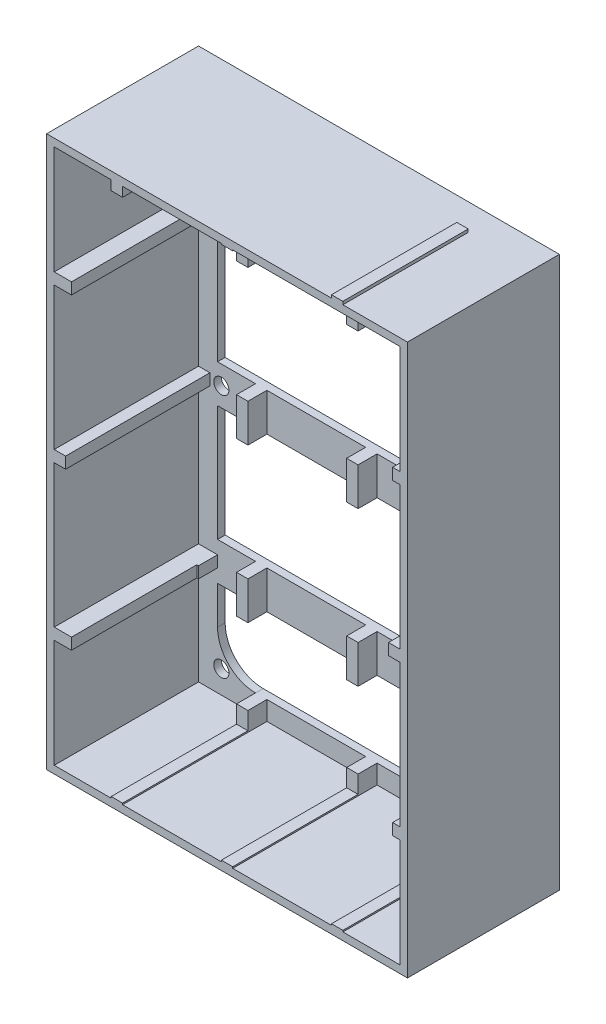
SolidWorks part; units mm, degrees
ref_plane "前视基准面" through (0, 0, 0) normal (0, 0, 1) x (1, 0, 0)
ref_plane "上视基准面" through (0, 0, 0) normal (0, 1, 0) x (1, 0, 0)
ref_plane "右视基准面" through (0, 0, 0) normal (1, 0, 0) x (0, 0, -1)
sketch "Sketch1" plane through (0, 0, 0) normal (0, 0, 1) x (1, 0, 0)
  line L1 (-47.5, 72.5) -> (47.5, 72.5)
  line L2 (-47.5, 72.5) -> (-47.5, -72.5)
  line L3 (-47.5, -72.5) -> (47.5, -72.5)
  line L4 (47.5, 72.5) -> (47.5, -72.5)
  line L5 (-47.5, 72.5) -> (47.5, -72.5) construction
  line L6 (-47.5, -72.5) -> (47.5, 72.5) construction
  point P0 (0, 0)
  dimension "D1" = 95
  dimension "D2" = 145
extrude "Boss-Extrude1" add sketch "Sketch1" along normal mid plane 40
sketch "Sketch2" plane through (0, 0, 20) normal (0, 0, 1) x (1, 0, 0)
  line L8 (45.5, -70.5) -> (45.5, 70.5)
  line L9 (45.5, 70.5) -> (-45.5, 70.5)
  line L10 (-45.5, 70.5) -> (-45.5, -70.5)
  line L11 (-45.5, -70.5) -> (45.5, -70.5)
  line L12 (45.5, -70.5) -> (45.5, 70.5)
  line L13 (45.5, 70.5) -> (-45.5, 70.5)
  line L14 (-45.5, 70.5) -> (-45.5, -70.5)
  line L15 (-45.5, -70.5) -> (45.5, -70.5)
  dimension "D1" = 2
extrude "Cut-Extrude1" cut sketch "Sketch2" against normal blind 40
ref_plane "Base" through (0, 0, -20) normal (0, 0, -1) x (-1, 0, 0)
sketch "Sketch3" plane through (0, 0, -20) normal (0, 0, -1) x (-1, 0, 0)
  line L0 (-45.5, 70.5) -> (45.5, 70.5) construction
  line L2 (42.5, -70.5) -> (42.5, 70.5) construction
  line L4 (-42.5, -70.5) -> (-42.5, 70.5) construction
  line L5 (42.5, -70.5) -> (-42.5, 70.5) construction
  line L6 (42.5, 70.5) -> (-42.5, -70.5) construction
  line L7 (-40.5, -35.5) -> (40.5, -35.5)
  line L8 (-40.5, -45.5) -> (40.5, -45.5)
  line L9 (-40.5, 5) -> (40.5, 5)
  line L10 (-40.5, -5) -> (40.5, -5)
  line L11 (45.5, -70.5) -> (-45.5, -70.5) construction
  line L12 (45.5, 70.5) -> (45.5, -70.5) construction
  line L13 (-45.5, -70.5) -> (-45.5, 70.5) construction
  line L14 (45.5, -70.5) -> (-45.5, -70.5)
  line L15 (-40.5, -65.5) -> (40.5, -65.5)
  line L16 (40.5, 65.5) -> (-40.5, 65.5)
  line L17 (40.5, -65.5) -> (40.5, 65.5)
  line L18 (-40.5, 65.5) -> (-40.5, -65.5)
  line L19 (-30.5, -65.5) -> (30.5, -65.5)
  line L20 (30.5, 65.5) -> (-30.5, 65.5)
  line L21 (40.5, -55.5) -> (40.5, -45.5)
  line L22 (-40.5, 55.5) -> (-40.5, 45.5)
  line L23 (45.5, 70.5) -> (45.5, -70.5)
  line L24 (-45.5, -70.5) -> (-45.5, 70.5)
  line L25 (-45.5, 70.5) -> (45.5, 70.5)
  line L26 (-40.5, 45.5) -> (40.5, 45.5)
  line L27 (-40.5, 35.5) -> (40.5, 35.5)
  line L28 (-62.7216, 0) -> (91.8842, 0) construction
  line L29 (-40.5, 35.5) -> (-40.5, 5)
  line L30 (40.5, 45.5) -> (40.5, 55.5)
  line L31 (40.5, 5) -> (40.5, 35.5)
  line L32 (-40.5, -5) -> (-40.5, -35.5)
  line L33 (-40.5, -45.5) -> (-40.5, -55.5)
  line L34 (40.5, -35.5) -> (40.5, -5)
  arc A0 (-30.5, -65.5) -> (-40.5, -55.5) centre (-30.5, -55.5) cw
  arc A1 (30.5, -65.5) -> (40.5, -55.5) centre (30.5, -55.5) ccw
  arc A2 (30.5, 65.5) -> (40.5, 55.5) centre (30.5, 55.5) cw
  arc A3 (-30.5, 65.5) -> (-40.5, 55.5) centre (-30.5, 55.5) ccw
  point P0 (0, 0)
  dimension "D3" = 10
  dimension "D1" = 85
  dimension "D4" = 10
  dimension "D5" = 20
  dimension "D6" = 5
  dimension "D2" = 5
extrude "Boss-Extrude2" add sketch "Sketch3" against normal blind 2
sketch "Sketch4" plane through (0, 0, -20) normal (0, 0, -1) x (-1, 0, 0)
  line L0 (-47.5, 72.5) -> (47.5, 72.5) construction
  line L1 (-47.5, -72.5) -> (-47.5, 72.5) construction
  line L2 (47.5, 72.5) -> (47.5, -72.5) construction
  line L3 (-75.8795, 0) -> (73.4613, 0) construction
  line L4 (47.5, 72.5) -> (47.5, -72.5) construction
  line L5 (-42.5, -70) -> (42.5, -70) construction
  line L6 (-42.5, -70) -> (-42.5, 70) construction
  line L7 (-42.5, 70) -> (42.5, 70) construction
  line L8 (42.5, -70) -> (42.5, 70) construction
  line L9 (-42.5, -70) -> (42.5, 70) construction
  line L10 (-42.5, 70) -> (42.5, -70) construction
  line L11 (-47.5, -72.5) -> (-47.5, 72.5) construction
  circle A0 centre (-39.5, 64.5) radius 2
  circle A1 centre (39.5, 64.5) radius 2
  circle A4 centre (-39.5, 0) radius 2
  circle A5 centre (39.5, 0) radius 2
  circle A6 centre (-39.5, -64.5) radius 2
  circle A7 centre (39.5, -64.5) radius 2
  point P21 (0, 0)
  dimension "D1" = 8
  dimension "D5" = 85
  dimension "D2" = 8
  dimension "D3" = 8
  dimension "D4" = 8
  dimension "D6" = 140
  dimension "D7" = 8
  dimension "D8" = 8
extrude "Cut-Extrude2" cut sketch "Sketch4" against normal up to next
sketch "Sketch6" plane through (0, 0, -18) normal (0, 0, 1) x (1, 0, 0)
  line L0 (-45.5, 70.5) -> (45.5, 70.5) construction
  line L1 (42.5, -68) -> (-42.5, -68) construction
  line L2 (42.5, -68) -> (42.5, 68) construction
  line L3 (42.5, 68) -> (-42.5, 68) construction
  line L4 (-42.5, -68) -> (-42.5, 68) construction
  line L5 (-30.5, 65.5) -> (30.5, 65.5) construction
  line L6 (-30.5, 68) -> (-27.5, 68)
  line L7 (-30.5, 70.5) -> (-27.5, 70.5)
  line L8 (-30.5, 70.5) -> (-30.5, 68)
  line L9 (-30.5, 68) -> (-27.5, 68)
  line L10 (-27.5, 70.5) -> (-27.5, 68)
  line L11 (0, 86.8311) -> (0, -114.9189) construction
  line L12 (-76.1678, 0) -> (120.2613, 0) construction
  line L13 (30.5, 68) -> (27.5, 68)
  line L14 (27.5, 70.5) -> (27.5, 68)
  line L15 (30.5, 70.5) -> (27.5, 70.5)
  line L16 (30.5, 70.5) -> (30.5, 68)
  line L17 (30.5, -70.5) -> (30.5, -68)
  line L18 (-1.5, 70.5) -> (1.5, 70.5)
  line L19 (-1.5, 70.5) -> (-1.5, 68)
  line L20 (-1.5, 68) -> (1.5, 68)
  line L21 (1.5, 70.5) -> (1.5, 68)
  line L22 (30.5, -70.5) -> (27.5, -70.5)
  line L23 (27.5, -70.5) -> (27.5, -68)
  line L24 (30.5, -68) -> (27.5, -68)
  line L25 (-1.5, -68) -> (1.5, -68)
  line L26 (1.5, -70.5) -> (1.5, -68)
  line L27 (-1.5, -70.5) -> (1.5, -70.5)
  line L28 (-1.5, -70.5) -> (-1.5, -68)
  line L29 (-30.5, -68) -> (-27.5, -68)
  line L30 (-27.5, -70.5) -> (-27.5, -68)
  line L31 (-30.5, -70.5) -> (-27.5, -70.5)
  line L32 (-30.5, -70.5) -> (-30.5, -68)
  line L33 (-45.5, 70.5) -> (-45.5, -70.5) construction
  line L34 (-45.5, 42) -> (-42.5, 42)
  line L35 (-45.5, 42) -> (-45.5, 39)
  line L36 (-45.5, 39) -> (-42.5, 39)
  line L37 (-42.5, 42) -> (-42.5, 39)
  line L38 (-45.5, -70.5) -> (-45.5, 70.5) construction
  line L39 (-45.5, 1.5) -> (-42.5, 1.5)
  line L40 (-45.5, 1.5) -> (-45.5, -1.5)
  line L41 (-45.5, -1.5) -> (-42.5, -1.5)
  line L42 (-42.5, 1.5) -> (-42.5, -1.5)
  line L43 (-33.759, -35.5) -> (-33.759, -45.5) construction
  line L44 (-45.5, -39) -> (-42.5, -39)
  line L45 (-45.5, -39) -> (-45.5, -42)
  line L46 (-45.5, -42) -> (-42.5, -42)
  line L47 (-42.5, -39) -> (-42.5, -42)
  line L48 (40.5, -35.5) -> (-40.5, -35.5) construction
  line L49 (-40.5, -45.5) -> (40.5, -45.5) construction
  line L50 (-33.759, 5) -> (-33.759, -5) construction
  line L51 (40.5, 5) -> (-40.5, 5) construction
  line L52 (-40.5, -5) -> (40.5, -5) construction
  line L53 (-34.8742, 45.5) -> (-34.8742, 35.5) construction
  line L54 (40.5, 45.5) -> (-40.5, 45.5) construction
  line L55 (-40.5, 35.5) -> (40.5, 35.5) construction
  line L56 (45.5, 39) -> (42.5, 39)
  line L57 (42.5, 42) -> (42.5, 39)
  line L58 (45.5, 42) -> (42.5, 42)
  line L59 (45.5, 42) -> (45.5, 39)
  line L60 (45.5, -1.5) -> (42.5, -1.5)
  line L61 (42.5, 1.5) -> (42.5, -1.5)
  line L62 (45.5, 1.5) -> (42.5, 1.5)
  line L63 (45.5, 1.5) -> (45.5, -1.5)
  line L64 (45.5, -42) -> (42.5, -42)
  line L65 (42.5, -39) -> (42.5, -42)
  line L66 (45.5, -39) -> (42.5, -39)
  line L67 (45.5, -39) -> (45.5, -42)
  line L68 (-30.5, 45.5) -> (-30.5, 35.5)
  line L69 (-30.5, 35.5) -> (-27.5, 35.5)
  line L70 (-27.5, 35.5) -> (-27.5, 45.5)
  line L71 (-27.5, 45.5) -> (-30.5, 45.5)
  line L72 (-30.5, 68) -> (-30.5, 65.5)
  line L73 (-1.5, 45.5) -> (1.5, 45.5)
  line L74 (-1.5, 45.5) -> (-1.5, 35.5)
  line L75 (-1.5, 35.5) -> (1.5, 35.5)
  line L76 (1.5, 45.5) -> (1.5, 35.5)
  line L77 (27.5, 45.5) -> (30.5, 45.5)
  line L78 (27.5, 45.5) -> (27.5, 35.5)
  line L79 (27.5, 35.5) -> (30.5, 35.5)
  line L80 (30.5, 45.5) -> (30.5, 35.5)
  line L81 (-30.5, 5) -> (-27.5, 5)
  line L82 (-30.5, 5) -> (-30.5, -5)
  line L83 (-30.5, -5) -> (-27.5, -5)
  line L84 (-27.5, 5) -> (-27.5, -5)
  line L85 (-1.5, 5) -> (1.5, 5)
  line L86 (-1.5, 5) -> (-1.5, -5)
  line L87 (-1.5, -5) -> (1.5, -5)
  line L88 (1.5, 5) -> (1.5, -5)
  line L89 (27.5, 5) -> (30.5, 5)
  line L90 (27.5, 5) -> (27.5, -5)
  line L91 (27.5, -5) -> (30.5, -5)
  line L92 (30.5, 5) -> (30.5, -5)
  line L93 (-30.5, -35.5) -> (-27.5, -35.5)
  line L94 (-30.5, -35.5) -> (-30.5, -45.5)
  line L95 (-30.5, -45.5) -> (-27.5, -45.5)
  line L96 (-27.5, -35.5) -> (-27.5, -45.5)
  line L97 (-1.5, -35.5) -> (1.5, -35.5)
  line L98 (-1.5, -35.5) -> (-1.5, -45.5)
  line L99 (-1.5, -45.5) -> (1.5, -45.5)
  line L100 (1.5, -35.5) -> (1.5, -45.5)
  line L101 (27.5, -35.5) -> (30.5, -35.5)
  line L102 (27.5, -35.5) -> (27.5, -45.5)
  line L103 (27.5, -45.5) -> (30.5, -45.5)
  line L104 (30.5, -35.5) -> (30.5, -45.5)
  line L105 (-30.5, 65.5) -> (-27.5, 65.5)
  line L106 (-27.5, 68) -> (-27.5, 65.5)
  line L107 (30.5, -65.5) -> (-30.5, -65.5) construction
  line L108 (-1.5, 68) -> (1.5, 68)
  line L109 (-1.5, 68) -> (-1.5, 65.5)
  line L110 (-1.5, 65.5) -> (1.5, 65.5)
  line L111 (1.5, 68) -> (1.5, 65.5)
  line L112 (27.5, 68) -> (30.5, 68)
  line L113 (27.5, 68) -> (27.5, 65.5)
  line L114 (27.5, 65.5) -> (30.5, 65.5)
  line L115 (30.5, 68) -> (30.5, 65.5)
  line L116 (-42.5, 42) -> (-40.5, 42)
  line L117 (-42.5, 42) -> (-42.5, 39)
  line L118 (-42.5, 39) -> (-40.5, 39)
  line L119 (-40.5, 42) -> (-40.5, 39)
  line L120 (42.5, 42) -> (40.5, 42)
  line L121 (42.5, 42) -> (42.5, 39)
  line L122 (42.5, 39) -> (40.5, 39)
  line L123 (40.5, 42) -> (40.5, 39)
  line L124 (-42.5, -39) -> (-40.5, -39)
  line L125 (-42.5, -39) -> (-42.5, -42)
  line L126 (-42.5, -42) -> (-40.5, -42)
  line L127 (-40.5, -39) -> (-40.5, -42)
  line L128 (42.5, -39) -> (40.5, -39)
  line L129 (42.5, -39) -> (42.5, -42)
  line L130 (42.5, -42) -> (40.5, -42)
  line L131 (40.5, -39) -> (40.5, -42)
  line L132 (30.5, -68) -> (27.5, -68)
  line L133 (30.5, -68) -> (30.5, -65.5)
  line L134 (30.5, -65.5) -> (27.5, -65.5)
  line L135 (27.5, -68) -> (27.5, -65.5)
  line L137 (1.5, -68) -> (-1.5, -68)
  line L138 (1.5, -68) -> (1.5, -65.5)
  line L139 (1.5, -65.5) -> (-1.5, -65.5)
  line L140 (-1.5, -68) -> (-1.5, -65.5)
  line L141 (-30.5, -68) -> (-27.5, -68)
  line L142 (-30.5, -68) -> (-30.5, -65.5)
  line L143 (-30.5, -65.5) -> (-27.5, -65.5)
  line L144 (-27.5, -68) -> (-27.5, -65.5)
  point P0 (0, 0)
  point P70 (-34.8742, 40.5)
  point P71 (-33.759, -40.5)
  line M9 (40.5, -35.5) -> (-40.5, -35.5)
  line M11 (-40.5, -5) -> (40.5, -5)
  line M13 (40.5, 5) -> (-40.5, 5)
  line M15 (-40.5, 35.5) -> (40.5, 35.5)
  line M17 (-30.5, 65.5) -> (30.5, 65.5)
  line M20 (40.5, 45.5) -> (-40.5, 45.5)
  line M23 (30.5, -65.5) -> (-30.5, -65.5)
  line M26 (-40.5, -45.5) -> (40.5, -45.5)
  line M28 (-45.5, 70.5) -> (-45.5, -70.5)
  line M29 (-45.5, -70.5) -> (45.5, -70.5)
  line M30 (45.5, -70.5) -> (45.5, 70.5)
  line M31 (45.5, 70.5) -> (-45.5, 70.5)
  dimension "D1" = 85
  dimension "D2" = 136
  dimension "D3" = 3
  dimension "D4" = 3
  dimension "D5" = 1.5
  dimension "D6" = 3
  dimension "D7" = 3
  dimension "D8" = 3
  dimension "D9" = 1.5
  dimension "D10" = 1.5
  dimension "D11" = 1.5
extrude "Boss-Extrude3" add sketch "Sketch6" along normal blind 5 contours L10 L8 L6 M31 | L106 L6 L72 M17 | L111 L20 L109 M17 | L21 L19 L20 M31 | L16 L14 L13 M31 | L115 L13 L113 M17 | L58 L57 L56 M30 | L120 L123 L122 L57 | L80 L78 M20 M15 | L70 L68 M15 M20 | L37 L34 L36 M28 | L119 L116 L37 L118 | L62 L61 L60 M30 | L92 L90 M13 M11 | L84 L82 M13 M11 | L42 L39 L41 M28 | L47 L44 L46 M28 | L127 L124 L47 L126 | L96 L94 M9 M26 | L104 L102 M9 M26 | L128 L131 L130 L65 | L66 L65 L64 M30 | L32 L30 L29 M29 | L29 L144 L142 M23 | L140 L25 L138 M23 | L28 L26 L25 M29 | L17 L24 L23 M29 | L135 L24 L133 M23 | L74 L75 L76 L73 | L88 L87 L86 L85 | L100 L99 L98 L97 region at (-29, 69.25, -18) region at (-29, 66.75, -18) region at (0, 69.25, -18) region at (0, 66.75, -18) region at (-44, 40.5, -18) region at (-41.5, 40.5, -18) region at (29, 69.25, -18) region at (29, 66.75, -18) region at (-44, 0, -18) region at (-44, -40.5, -18) region at (44, 40.5, -18) region at (-41.5, -40.5, -18) region at (41.5, 40.5, -18) region at (44, 0, -18) region at (-29, -69.25, -18) region at (-29, -66.75, -18) region at (44, -40.5, -18) region at (0, -69.25, -18) region at (41.5, -40.5, -18) region at (0, -66.75, -18) region at (29, -69.25, -18) region at (29, -66.75, -18) region at (-29, 40.5, -18) region at (29, 40.5, -18) region at (-29, 0, -18) region at (29, 0, -18) region at (-29, -40.5, -18) region at (29, -40.5, -18)
sketch "Sketch7" plane through (0, 0, -13) normal (0, 0, 1) x (1, 0, 0)
  line L4 (-27.5, 70.5) -> (-27.5, 65.5) construction
  line L5 (-30.5, 70.5) -> (-27.5, 70.5)
  line L6 (-30.5, 70.5) -> (-30.5, 68)
  line L7 (-30.5, 68) -> (-27.5, 68)
  line L99 (-27.5, 70.5) -> (-27.5, 68)
  line L100 (43.5939, -70.1248) -> (-40.9521, -70.1248) construction
  line L101 (43.5939, -70.1248) -> (43.5939, 74.6484) construction
  line L102 (43.5939, 74.6484) -> (-40.9521, 65.8752) construction
  line L103 (-40.9521, -70.1248) -> (-40.9521, 65.8752) construction
  line L104 (43.5939, -70.1248) -> (-40.9521, 65.8752) construction
  line L105 (43.5939, 74.6484) -> (-40.9521, -70.1248) construction
  line L106 (1.5, 70.5) -> (1.5, 65.5) construction
  line L107 (-1.5, 70.5) -> (1.5, 70.5)
  line L108 (-1.5, 70.5) -> (-1.5, 70.2804)
  line L109 (-1.5, 70.2804) -> (1.5, 70.2804)
  line L110 (1.5, 70.5) -> (1.5, 70.2804)
  line L111 (30.5, 70.5) -> (30.5, 65.5) construction
  line L112 (27.5, 70.5) -> (30.5, 70.5)
  line L113 (27.5, 70.5) -> (27.5, 73.2897)
  line L114 (27.5, 73.2897) -> (30.5, 73.2897)
  line L115 (30.5, 70.5) -> (30.5, 73.2897)
  line L116 (-45.5, 39) -> (-40.5, 39) construction
  line L117 (-45.5, 42) -> (-40.9521, 42)
  line L118 (-45.5, 42) -> (-45.5, 39)
  line L119 (-45.5, 39) -> (-40.9521, 39)
  line L120 (-40.9521, 42) -> (-40.9521, 39)
  line L121 (-45.5, -42) -> (-40.5, -42) construction
  line L122 (45.5, 42) -> (43.5939, 42)
  line L123 (45.5, 42) -> (45.5, 39)
  line L124 (45.5, 39) -> (43.5939, 39)
  line L125 (43.5939, 42) -> (43.5939, 39)
  line L126 (45.5, 1.5) -> (42.5, 1.5)
  line L127 (45.5, 1.5) -> (45.5, -1.5)
  line L128 (45.5, -1.5) -> (42.5, -1.5)
  line L129 (42.5, 1.5) -> (42.5, -1.5)
  line L130 (-45.5, -39) -> (-40.9521, -39)
  line L131 (-45.5, -39) -> (-45.5, -42)
  line L132 (-45.5, -42) -> (-40.9521, -42)
  line L133 (-40.9521, -39) -> (-40.9521, -42)
  line L134 (30.5, -70.5) -> (30.5, -65.5) construction
  line L135 (45.5, -39) -> (43.5939, -39)
  line L136 (45.5, -39) -> (45.5, -42)
  line L137 (45.5, -42) -> (43.5939, -42)
  line L138 (43.5939, -39) -> (43.5939, -42)
  line L139 (27.5, -70.5) -> (30.5, -70.5)
  line L140 (27.5, -70.5) -> (27.5, -70.1248)
  line L141 (27.5, -70.1248) -> (30.5, -70.1248)
  line L142 (30.5, -70.5) -> (30.5, -70.1248)
  line L143 (-1.5, -70.5) -> (-1.5, -65.5) construction
  line L144 (1.5, -70.5) -> (-1.5, -70.5)
  line L145 (1.5, -70.5) -> (1.5, -70.1248)
  line L146 (1.5, -70.1248) -> (-1.5, -70.1248)
  line L147 (-1.5, -70.5) -> (-1.5, -70.1248)
  line L149 (-27.5, -70.5) -> (-30.5, -70.5)
  line L150 (-27.5, -70.5) -> (-27.5, -70.1248)
  line L151 (-27.5, -70.1248) -> (-30.5, -70.1248)
  line L152 (-30.5, -70.5) -> (-30.5, -70.1248)
  line L153 (-45.5, 1.5) -> (-42.5, 1.5)
  line L154 (-45.5, 1.5) -> (-45.5, -1.5)
  line L155 (-45.5, -1.5) -> (-42.5, -1.5)
  line L156 (-42.5, 1.5) -> (-42.5, -1.5)
  circle A0 centre (-39.5, 64.5) radius 2 construction
  point P14 (0, 0)
  dimension "D2" = 85
  dimension "D3" = 136
extrude "Boss-Extrude4" add sketch "Sketch7" along normal up to surface (33 mm away) up to face at (0, 0, 20)
